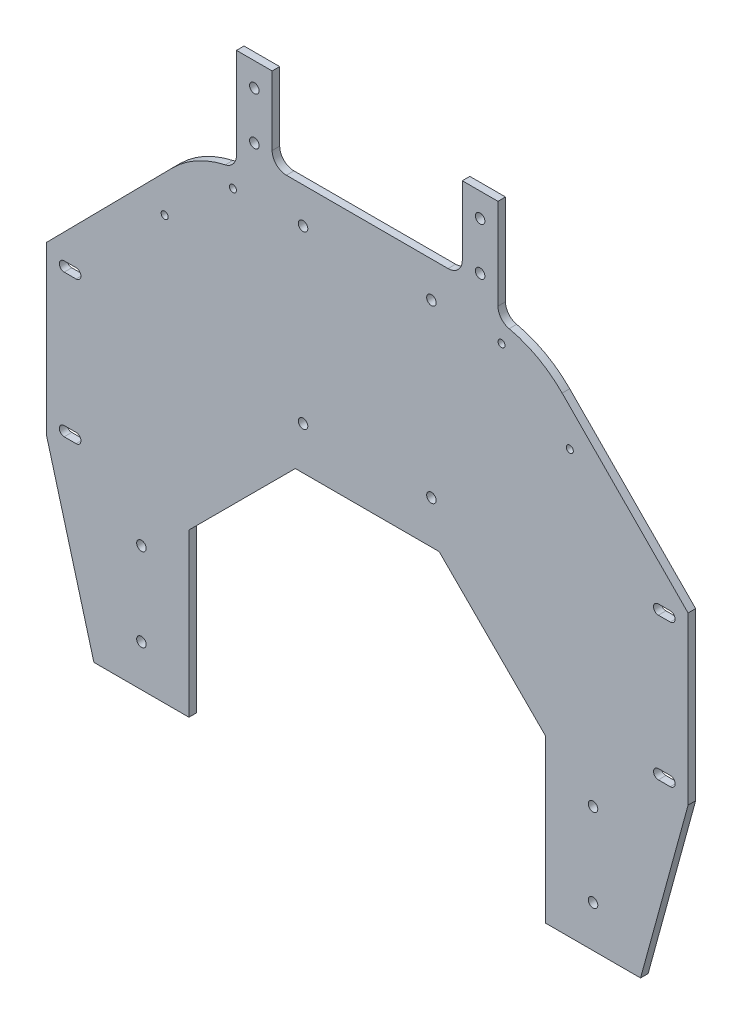
SolidWorks part; units mm, degrees
ref_plane "Front Plane" through (0, 0, 0) normal (0, 0, 1) x (1, 0, 0)
ref_plane "Top Plane" through (0, 0, 0) normal (0, 1, 0) x (1, 0, 0)
ref_plane "Right Plane" through (0, 0, 0) normal (1, 0, 0) x (0, 0, -1)
sketch "Sketch1" plane through (0, 0, 0) normal (0, 0, 1) x (1, 0, 0)
  line L1 (-100, -75) -> (100, -75)
  line L2 (-100, -75) -> (-100, 75)
  line L3 (-100, 75) -> (100, 75)
  line L4 (100, -75) -> (100, 75)
  line L5 (-100, -75) -> (100, 75) construction
  line L6 (-100, 75) -> (100, -75) construction
  line L8 (-47.5, 40) -> (47.5, 40) construction
  line L9 (0, 75) -> (0, -75) construction
  line L10 (-27, -52) -> (27, -52) construction
  line L11 (-27, -52) -> (-27, 20) construction
  line L12 (-27, 20) -> (27, 20) construction
  line L13 (27, -52) -> (27, 20) construction
  line L14 (-27, -52) -> (27, 20) construction
  line L15 (-27, 20) -> (27, -52) construction
  line L23 (-55, 70) -> (55, 70)
  line L24 (-55, 70) -> (-55, -70)
  line L25 (-55, -70) -> (55, -70)
  line L26 (55, 70) -> (55, -70)
  line L27 (-55, 70) -> (55, -70) construction
  line L28 (-55, -70) -> (55, 70) construction
  line L29 (-40, 70) -> (40, 70)
  line L30 (-40, 70) -> (-40, 35)
  line L31 (-40, 35) -> (40, 35)
  line L32 (40, 70) -> (40, 35)
  line L33 (-40, 70) -> (40, 35) construction
  line L34 (-40, 35) -> (40, 70) construction
  circle A2 centre (-47.5, 40) radius 2
  circle A3 centre (47.5, 40) radius 2
  circle A4 centre (-27, 20) radius 2
  circle A5 centre (27, 20) radius 2
  circle A6 centre (27, -52) radius 2
  circle A7 centre (-27, -52) radius 2
  circle A8 centre (-47.5, 60) radius 2
  circle A9 centre (47.5, 60) radius 2
  point P0 (0, 0)
  point P15 (0, 40)
  point P18 (0, -16)
  point P56 (0, 0)
  point P63 (0, 52.5)
  dimension "D3" = 4
  dimension "D4" = 20
  dimension "D5" = 4
  dimension "D8" = 4
  dimension "D1" = 150
  dimension "D2" = 200
  dimension "D6" = 72
  dimension "D7" = 54
  dimension "D14" = 30
  dimension "D15" = 140
  dimension "D16" = 110
  dimension "D17" = 95
  dimension "D18" = 20
  dimension "D19" = 35
  dimension "D20" = 80
extrude "Boss-Extrude1" add sketch "Sketch1" along normal blind 3.175 contours L23 L32 L31 L30 L24 L25 L26 A7 A6 A5 A4 A3 A2 region at (0, -11.8972, 0)
sketch "Sketch2" plane through (0, 0, 0) normal (0, 0, 1) x (1, 0, 0)
  line L0 (-55, -70) -> (-102.6256, -117.6256) construction
  line L1 (-55, 70) -> (-55, -70) construction
  line L2 (-55, -45.2513) -> (-115, -105.2513)
  line L3 (-30.2513, -70) -> (-90.2513, -130)
  line L4 (-55, -70) -> (55, -70) construction
  line L5 (-115, -105.2513) -> (-90.2513, -130)
  line L6 (-115, -105.2513) -> (-115, -183)
  line L7 (-75, -114.7487) -> (-75, -183)
  line L8 (-75, -183) -> (-115, -183)
  line L9 (0, 75) -> (0, -75) construction
  line L10 (-55, -45.2513) -> (-30.2513, -70)
  line L11 (-55, 70) -> (-55, -70) construction
  line L12 (-75, -183) -> (-115, -183) construction
  line L13 (-55, -70) -> (55, -70) construction
  line L14 (-55, 70) -> (-55, -70) construction
  circle A0 centre (-95, -130.5) radius 2
  circle A1 centre (-95, -165.5) radius 2
  dimension "D5" = 4
  dimension "D6" = 4
  dimension "D1" = 135
  dimension "D2" = 35
  dimension "D3" = 40
  dimension "D4" = 75
extrude "Boss-Extrude2" add sketch "Sketch2" along normal blind 3.175 contours L8 L7 L3 L5 L6 | L10 L2 L5 L3 region at (-72.6256, -87.6256, 0) region at (-95.7404, -150.8984, 0)
mirror "Mirror1" about plane through (0, 0, 0) normal (1, 0, 0) of "Boss-Extrude2"
sketch "Sketch3" plane through (0, 0, 3.175) normal (0, 0, 1) x (1, 0, 0)
  line L0 (0, 0) -> (0, 95.843) construction
  line L1 (-50, -18) -> (-85.2385, -5.1742) construction
  line L2 (-50, -18) -> (-56.5118, 18.9303) construction
  line L3 (-50, -18) -> (-87.5, -18) construction
  circle A0 centre (-50, -18) radius 30 construction
  circle A1 centre (-50, -18) radius 45
  circle A2 centre (-50, -18) radius 37.5 construction
  circle A3 centre (-85.2385, -5.1742) radius 1.4732
  circle A4 centre (-56.5118, 18.9303) radius 1.4732
  circle A5 centre (-47.5, 40) radius 2 construction
  circle A6 centre (56.5118, 18.9303) radius 1.4732
  circle A7 centre (85.2385, -5.1742) radius 1.4732
  circle A8 centre (50, -18) radius 45
  point P4 (-80.5, -63.0002)
  point P13 (-80.5, -31.4602)
  point P23 (0, 0)
  point P24 (-80.5, -21)
  line M5 (-30.2513, -70) -> (30.2513, -70)
  line M6 (30.2513, -70) -> (75, -114.7487)
  line M10 (115, -105.2513) -> (55, -45.2513)
  line M11 (55, -45.2513) -> (55, 70)
  line M13 (40, 70) -> (40, 35)
  line M14 (40, 35) -> (-40, 35)
  line M15 (-40, 35) -> (-40, 70)
  line M17 (-55, 70) -> (-55, -45.2513)
  line M18 (-55, -45.2513) -> (-115, -105.2513)
  line M22 (-75, -114.7487) -> (-30.2513, -70)
  circle M23 centre (-47.5, 40) radius 2
  circle M24 centre (47.5, 40) radius 2
  circle M25 centre (-27, 20) radius 2
  circle M26 centre (27, 20) radius 2
  circle M27 centre (27, -52) radius 2
  circle M28 centre (-27, -52) radius 2
  dimension "D1" = 60
  dimension "D3" = 7.5
  dimension "D4" = 58
  dimension "D8" = 2.9464
  dimension "D5" = 20
  dimension "D6" = 80
  dimension "D7" = 100
  dimension "D2" = 15
extrude "Boss-Extrude3" add sketch "Sketch3" against normal up to surface (3.175 mm away) contours A1 A4 A3 M17 M18 | A1 M15 M17 M18 M22 M5 M14 M28 M25 M23 | A8 M10 M11 M13 M14 M5 M6 M27 M26 M24 | A8 A6 A7 M11 M10 region at (-34.4822, -19.2379, 3.175) region at (-72.4185, -16.3072, 3.175) region at (72.4185, -16.3072, 3.175) region at (34.4822, -19.2379, 3.175) up to face at (0, -58.4724, 0)
sketch "Sketch4" plane through (0, 0, 3.175) normal (0, 0, 1) x (1, 0, 0)
  line L0 (-135, -110) -> (-115, -183)
  line L1 (-60, -110) -> (-115, -110) construction
  line L2 (-60, -110) -> (-60, -40)
  line L3 (-60, -40) -> (-106.8836, -40)
  line L4 (-135, -110) -> (-135, -40)
  line L5 (-60, -110) -> (-135, -40) construction
  line L6 (-60, -40) -> (-135, -110) construction
  line L8 (-115, -105.2513) -> (-115, -183) construction
  line L9 (-115, -110) -> (-115, -183)
  line L10 (-111.1989, -110) -> (-135, -110) construction
  line L11 (-135, -40) -> (-82.0098, 13.6287)
  line L12 (-106.8836, -40) -> (-94.0818, -27.044)
  line L13 (-106.8836, -40) -> (-135, -40) construction
  line L14 (-135, -75) -> (-60, -75) construction
  line L15 (-125, -40) -> (-125, -75) construction
  line L18 (-60, -110) -> (-60, -105.2513)
  line L19 (-60, -105.2513) -> (-115, -105.2513)
  line L20 (-115, -110) -> (-115, -105.2513)
  line L21 (-60, -110) -> (-115, -105.2513) construction
  line L22 (-60, -105.2513) -> (-115, -110) construction
  line L23 (-122.5, -45) -> (-127.5, -45) construction
  line L24 (-122.5, -47.05) -> (-127.5, -47.05)
  line L25 (-122.5, -42.95) -> (-127.5, -42.95)
  line L26 (-122.5, -105) -> (-127.5, -105) construction
  line L27 (-122.5, -102.95) -> (-127.5, -102.95)
  line L28 (-122.5, -107.05) -> (-127.5, -107.05)
  circle A0 centre (-56.5118, 18.9303) radius 1.4732
  circle A1 centre (-56.5118, 18.9303) radius 1.4732 construction
  arc A2 (-55, 26.7214) -> (-68.6858, -58.937) centre (-50, -18) ccw construction
  arc A3 (-94.0818, -27.044) -> (-82.0098, 13.6287) centre (-50, -18) cw
  circle A4 centre (-125, -45) radius 2.05 construction
  circle A6 centre (-125, -105) radius 2.05 construction
  arc A7 (-122.5, -47.05) -> (-122.5, -42.95) centre (-122.5, -45) ccw
  arc A8 (-127.5, -42.95) -> (-127.5, -47.05) centre (-127.5, -45) ccw
  arc A9 (-122.5, -102.95) -> (-122.5, -107.05) centre (-122.5, -105) cw
  arc A10 (-127.5, -107.05) -> (-127.5, -102.95) centre (-127.5, -105) cw
  point P0 (-97.5, -75)
  point P36 (-87.5, -107.6256)
  point P38 (-125, -45)
  point P48 (-125, -105)
  arc M14 (-55, 26.7214) -> (-68.6858, -58.937) centre (-50, -18) ccw
  line M15 (-68.6858, -58.937) -> (-115, -105.2513)
  line M16 (-115, -105.2513) -> (-115, -183)
  dimension "D7" = 4.1
  dimension "D9" = 2.05
  dimension "D1" = 60
  dimension "D2" = 40
  dimension "D3" = 75
  dimension "D4" = 70
  dimension "D6" = 20
  dimension "D8" = 10
  dimension "D10" = 5
  dimension "D11" = 5
extrude "Boss-Extrude4" add sketch "Sketch4" against normal up to surface (3.175 mm away) contours L11 L4 L0 A8 L25 A7 L24 L28 A10 L27 A9 M16 M15 M14 | L12 L3 M14 region at (-111.7558, -72.1659, 3.175) region at (-96.9601, -35.7754, 3.175) up to face at (0, -50.8008, 0)
mirror "Mirror2" about plane through (0, 0, 0) normal (1, 0, 0) of "Boss-Extrude4"
fillet "Fillet1" radius 6 4 edges at (-55, 26.7214, 1.5875) (-40, 35, 1.5875) (40, 35, 1.5875) (55, 26.7214, 1.5875)
